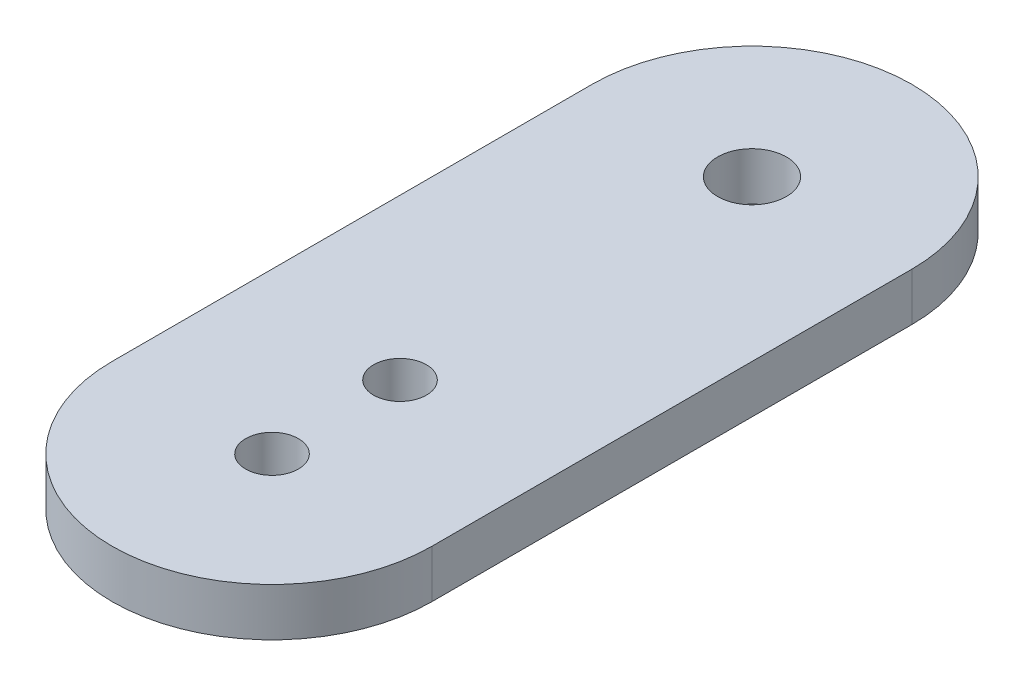
SolidWorks part; units mm, degrees
material "Acrylic (Medium-high impact)"
ref_plane "Front Plane" through (0, 0, 0) normal (0, 0, 1) x (1, 0, 0)
ref_plane "Top Plane" through (0, 0, 0) normal (0, 1, 0) x (1, 0, 0)
ref_plane "Right Plane" through (0, 0, 0) normal (1, 0, 0) x (0, 0, -1)
sketch "Sketch2" plane through (0, 0, 0) normal (0, 1, 0) x (1, 0, 0)
  line L0 (0, 0) -> (0, 30) construction
  line L1 (-10, 0) -> (-10, 30)
  line L2 (10, 0) -> (10, 30)
  arc A0 (-10, 0) -> (10, 0) centre (0, 0) ccw
  arc A1 (10, 30) -> (-10, 30) centre (0, 30) ccw
  point P3 (0, 15)
  dimension "D2" = 10
  dimension "D1" = 30
extrude "Boss-Extrude1" add sketch "Sketch2" along normal blind 3
sketch "Sketch3" plane through (0, 3, 0) normal (0, 1, 0) x (1, 0, 0)
  circle A0 centre (0, 0) radius 1.65
  circle A1 centre (0, 8) radius 1.65
  circle A2 centre (0, 30) radius 2.15
  dimension "D1" = 3.3
  dimension "D2" = 3.3
  dimension "D4" = 4.3
  dimension "D3" = 8
extrude "Cut-Extrude1" cut sketch "Sketch3" against normal blind 3
sketch "Sketch4" plane through (0, 0, 0) normal (0, -1, 0) x (1, 0, 0)
  line L0 (-10, -19.167) -> (10, -19.167) construction
  line L1 (-10, -30) -> (-10, 0) construction
  line L2 (10, 0) -> (10, -30) construction
  text T0 "Group 3" font "Century Gothic" height in points 9
extrude "Cut-Extrude2" cut sketch "Sketch4" against normal blind 0.5
